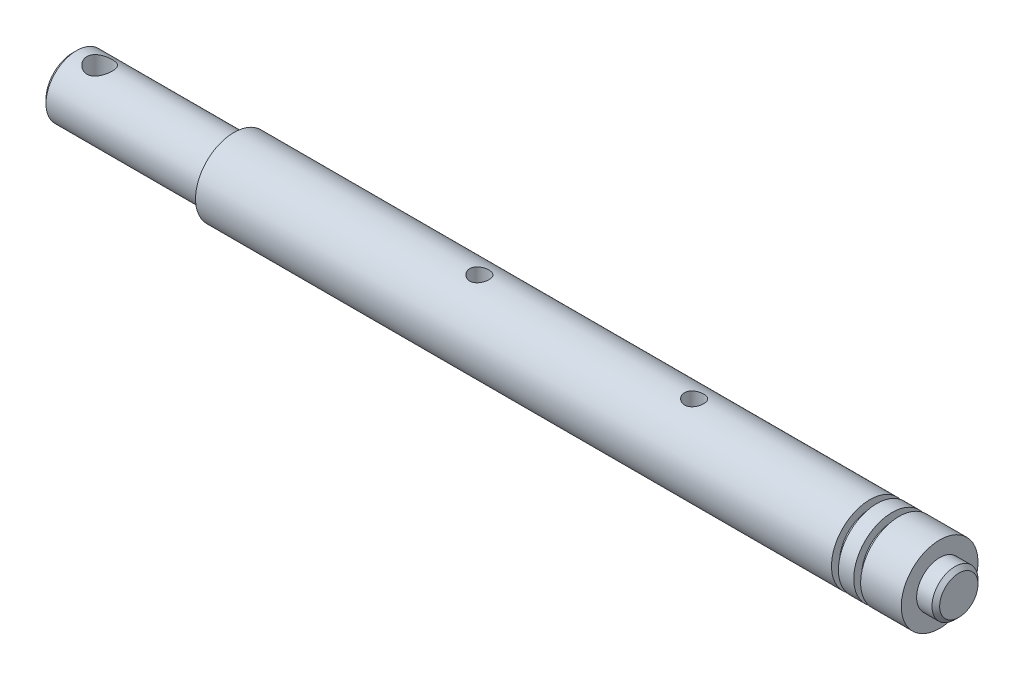
SolidWorks part; units mm, degrees
note: The reader was unsure of these and kept them because the rebuilt part matched: shared geometry of "草图7<2>".
material "普通碳钢"
ref_plane "前视基准面" through (0, 0, 0) normal (0, 0, 1) x (1, 0, 0)
ref_plane "上视基准面" through (0, 0, 0) normal (0, 1, 0) x (1, 0, 0)
ref_plane "右视基准面" through (0, 0, 0) normal (1, 0, 0) x (0, 0, -1)
other "45"
sketch "草图1" plane through (0, 0, 0) normal (1, 0, 0) x (0, 0, -1)
  circle A0 centre (0, 0) radius 4
  dimension "D1" = 8
extrude "凸台-拉伸1" add sketch "草图1" along normal blind 21
sketch "草图2" plane through (21, 0, 0) normal (1, 0, 0) x (0, 0, -1)
  circle A0 centre (0, 0) radius 5
  dimension "D1" = 10
extrude "凸台-拉伸2" add sketch "草图2" along normal up to surface (92 mm away)
ref_plane "基准面1" through (0, 7, 0) normal (0, 1, 0) x (1, 0, 0)
sketch "草图3" plane through (0, 7, 0) normal (0, 1, 0) x (1, 0, 0)
  line L0 (21, 4) -> (21, -4) construction
  line L1 (0, 4) -> (0, -4) construction
  circle A0 centre (3.5, 0) radius 1.65
  dimension "D1" = 3.3
  dimension "D2" = 21
  dimension "D3" = 3.5
extrude "切除-拉伸1" cut sketch "草图3" against normal blind 20
cosmetic thread "装饰螺纹线1" parameters "D2"=4
ref_plane "基准面3" through (101.5, 0, 0) normal (-1, 0, 0) x (0, 0, 1)
sketch "草图7" plane through (101.5, 0, 0) normal (-1, 0, 0) x (0, 0, 1)
  circle A0 centre (0, 0) radius 5 construction
  circle A1 centre (0, 0) radius 5
  circle A2 centre (0, 0) radius 3.95
  dimension "D1" = 7.9
extrude "切除-拉伸4" cut sketch "草图7" against normal blind 0.9 from surface at -5.3
sketch "草图8" plane through (113, 0, 0) normal (1, 0, 0) x (0, 0, -1)
  circle A0 centre (0, 0) radius 3
  dimension "D1" = 6
extrude "凸台-拉伸3" add sketch "草图8" along normal blind 2.5
chamfer "倒角1" distance 0.5 angle 45 2 edges at (0, 0, -4) (115.5, 0, -3)
ref_plane "基准面4" through (0, 5, 0) normal (0, 1, 0) x (1, 0, 0)
sketch "草图9" plane through (0, 5, 0) normal (0, 1, 0) x (1, 0, 0)
  line L1 (21, 5) -> (21, -5) construction
  circle A0 centre (81, 0) radius 1.25
  circle A1 centre (53, 0) radius 1.25
  dimension "D1" = 2.5
  dimension "D3" = 2.5
  dimension "D2" = 32
  dimension "D4" = 28
extrude "切除-拉伸5" cut sketch "草图9" against normal blind 7
cosmetic thread "装饰螺纹线2" parameters "D2"=3
cosmetic thread "装饰螺纹线3" parameters "D2"=3
extrude "切除-拉伸6" cut sketch "草图7<2>" along normal blind 0.9 from surface
sketch "草图7<2>" plane through (101.5, 0, 0) normal (-1, 0, 0) x (0, 0, 1) same geometry as "草图7"
